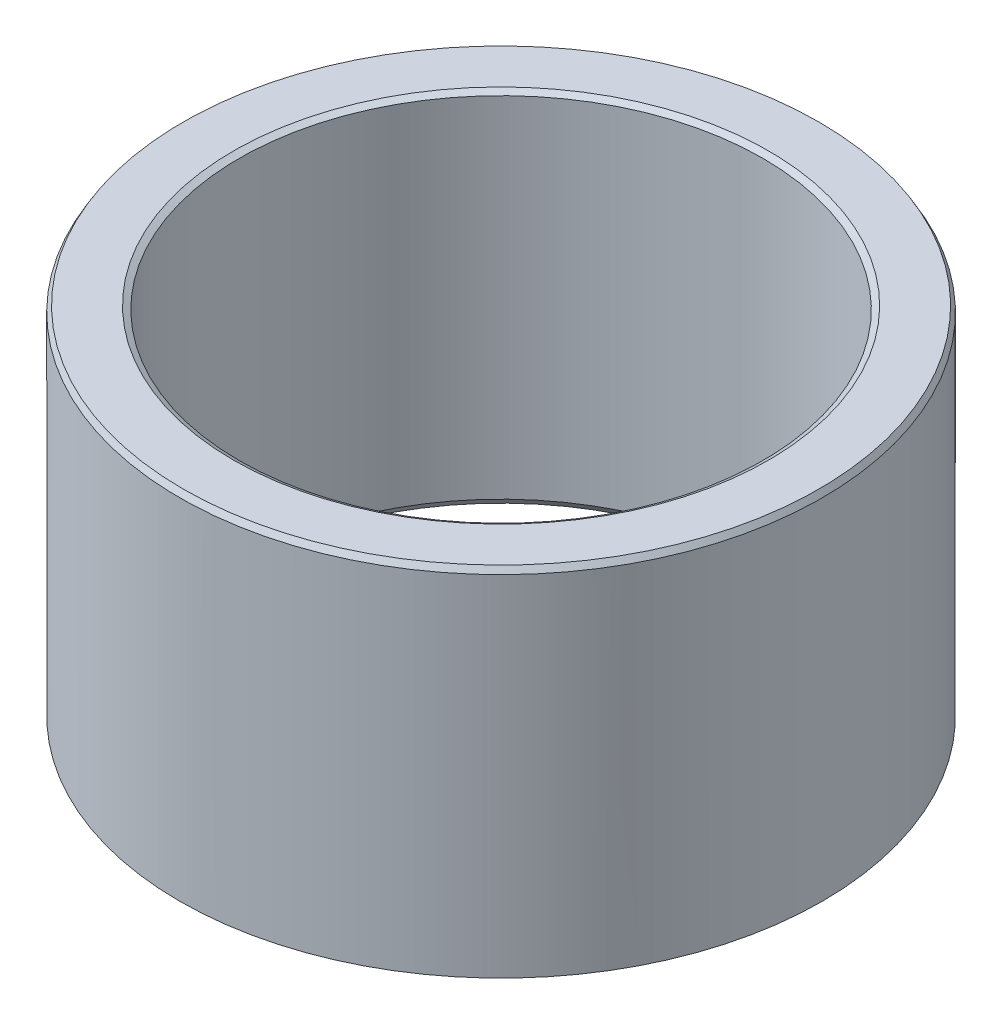
SolidWorks part; units mm, degrees
ref_plane "Front Plane" through (0, 0, 0) normal (0, 0, 1) x (1, 0, 0)
ref_plane "Top Plane" through (0, 0, 0) normal (0, 1, 0) x (1, 0, 0)
ref_plane "Right Plane" through (0, 0, 0) normal (1, 0, 0) x (0, 0, -1)
sketch "Sketch1" plane through (0, 0, 0) normal (0, 1, 0) x (1, 0, 0)
  circle A0 centre (0, 0) radius 52.5
  dimension "SLEEVE_OD" = 105
extrude "Boss-Extrude1" add sketch "Sketch1" along normal blind 58.6155
sketch "Sketch2" plane through (0, 0, 0) normal (0, 1, 0) x (1, 0, 0)
  circle A0 centre (0, 0) radius 42.7838
  dimension "BORE_D" = 85.5676
extrude "Cut-Extrude1" cut sketch "Sketch2" along normal through all
chamfer "Chamfer1" distance 0.9605 angle 30 4 edges at (0, 58.6155, 42.7838) (0, 0, 42.7838) (0, 0, 52.5) (0, 58.6155, 52.5) first distance on face at (0, 58.6155, 42.7838) first distance on face at (0, 0, 42.7838) first distance on face at (0, 58.6155, 52.5)
